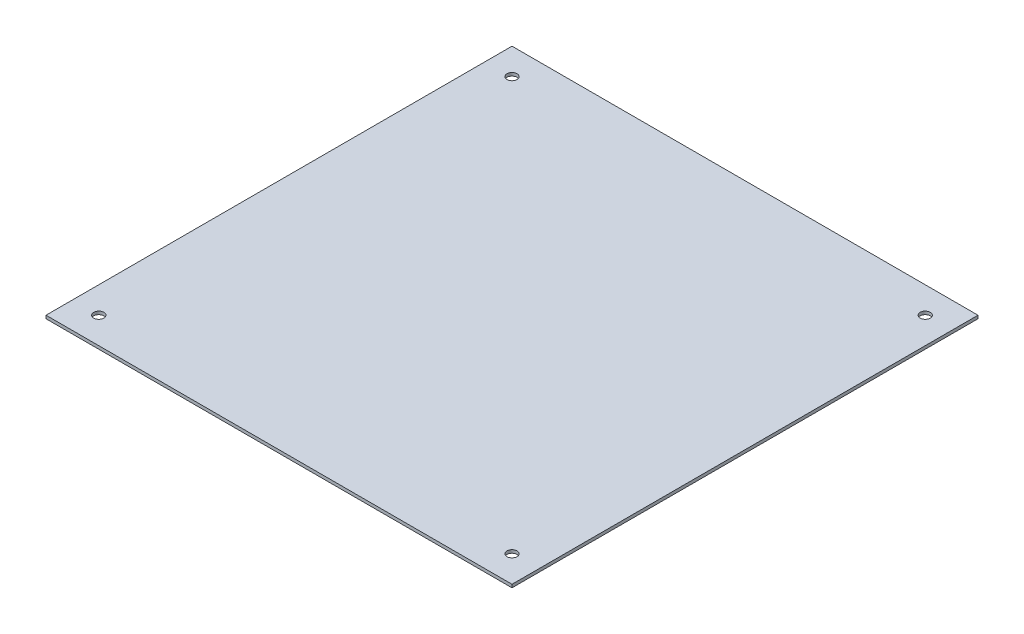
SolidWorks part; units mm, degrees
material "1023 Chapa de acero al carbono (SS)"
ref_plane "Alzado" through (0, 0, 0) normal (0, 0, 1) x (1, 0, 0)
ref_plane "Planta" through (0, 0, 0) normal (0, 1, 0) x (1, 0, 0)
ref_plane "Vista lateral" through (0, 0, 0) normal (1, 0, 0) x (0, 0, -1)
sketch "Sketch1" plane through (0, 0, 0) normal (0, 1, 0) x (1, 0, 0)
  line L1 (-150, -150) -> (150, -150)
  line L2 (-150, -150) -> (-150, 150)
  line L3 (-150, 150) -> (150, 150)
  line L4 (150, -150) -> (150, 150)
  line L5 (-150, -150) -> (150, 150) construction
  line L6 (-150, 150) -> (150, -150) construction
  point P0 (0, 0)
  dimension "D1" = 300
  dimension "D2" = 300
base flange "Base-Flange1" sketch "Sketch1" thickness 2 reverse thickness direction no parameters "D1"=1
hole_wizard "Ø6.5 (6.5) Diameter Hole1" positions "Sketch10" profile "Sketch11" hole size "Ø6.5" standard "ISO" end condition up to next
sketch "Sketch10" plane through (0, 0, 0) normal (0, 1, 0) x (1, 0, 0)
  line L0 (150, 150) -> (-150, 150) construction
  line L1 (-150, 150) -> (-150, -150) construction
  line L2 (150, -150) -> (150, 150) construction
  line L3 (-150, -150) -> (150, -150) construction
  point P0 (-133, 133)
  point P7 (133, 133)
  point P8 (133, -133)
  point P9 (-133, -133)
  dimension "D3" = 17
  dimension "D4" = 17
  dimension "D5" = 17
  dimension "D6" = 17
  dimension "D1" = 2
  dimension "D2" = 2
sketch "Sketch11" plane through (-133, 0, -133) normal (1, 0, 0) x (0, 0, 1)
  line L0 (0, 0) -> (0, 2)
  line L1 (0, 2) -> (3.25, 2)
  line L2 (3.25, 2) -> (3.25, 0)
  line L5 (3.25, 0) -> (0, 0)
  line L11 (0, -6.35) -> (0, 107.95) construction
  dimension "Diámetro de taladro hasta el siguiente" = 6.5
  dimension "Profundidad de taladro hasta el siguiente" = 2
sketch "Sketch3" [suppressed] plane through (0, 0, 0) normal (0, 1, 0) x (1, 0, 0)
sketch "Sketch5" [suppressed] plane through (0, 0, 0) normal (0, 1, 0) x (1, 0, 0)
sheet metal parameters "Sheet-Metal2" thickness 2 parameters "D1"=1
flat pattern "Flat-Pattern2" [suppressed]
sketch "Sketch7" plane through (0, 0, 0) normal (0, 1, 0) x (1, 0, 0)
sketch3d "Sketch9" [suppressed]
  line L0 (-200, -200, 0) -> (-200, 200, 0) construction
  line L1 (200, -200, 0) -> (200, 200, 0) construction
  line L2 (-200, -200, 0) -> (200, -200, 0) construction
  line L3 (-200, 200, 0) -> (200, 200, 0) construction
sheet metal parameters "Sheet-Metal3" thickness 2 parameters "D1"=1
flat pattern "Flat-Pattern2"
sketch "Sketch7"
sketch3d "Sketch9" [suppressed]
  line L0 (-150, -150, 0) -> (-150, 150, 0) construction
  line L1 (150, -150, 0) -> (150, 150, 0) construction
  line L2 (-150, -150, 0) -> (150, -150, 0) construction
  line L3 (-150, 150, 0) -> (150, 150, 0) construction
